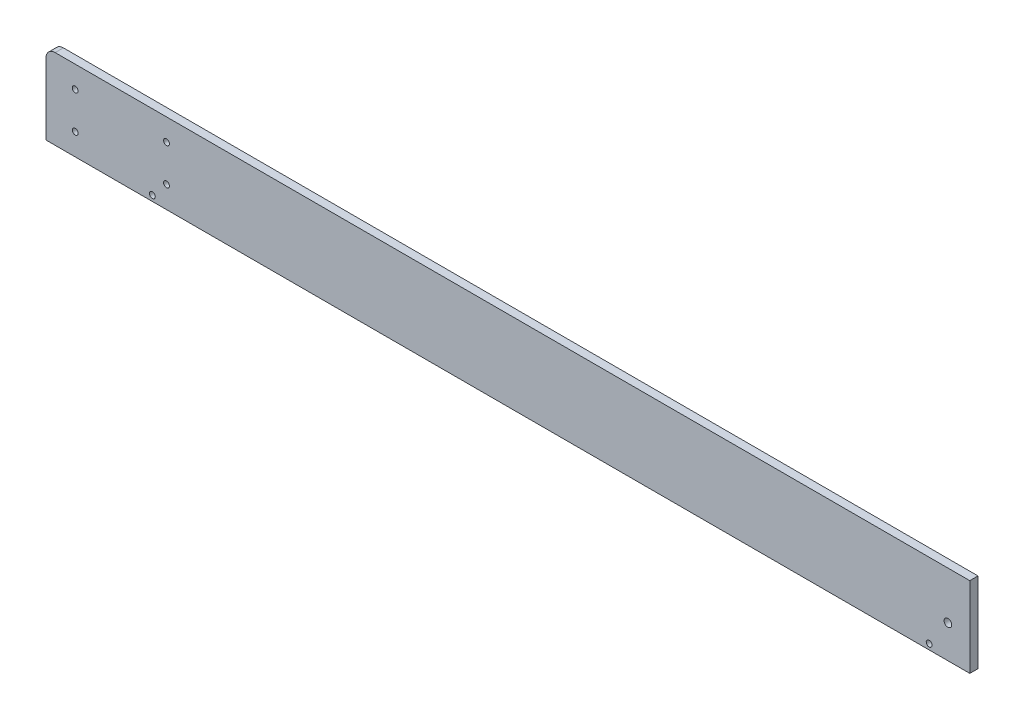
SolidWorks part; units mm, degrees
ref_plane "Front Plane" through (0, 0, 0) normal (0, 0, 1) x (1, 0, 0)
ref_plane "Top Plane" through (0, 0, 0) normal (0, 1, 0) x (1, 0, 0)
ref_plane "Right Plane" through (0, 0, 0) normal (1, 0, 0) x (0, 0, -1)
sketch "Sketch1" plane through (0, 0, 0) normal (0, 0, 1) x (1, 0, 0)
  line L0 (-253, 0) -> (-154.8681, 0) construction
  line L1 (-253, -22) -> (253, -22)
  line L2 (-253, -22) -> (-253, 22)
  line L3 (-253, 22) -> (253, 22)
  line L4 (253, -22) -> (253, 22)
  line L5 (-253, -22) -> (253, 22) construction
  line L6 (-253, 22) -> (253, -22) construction
  line L7 (-247, 6.6679) -> (-247, 39) construction
  circle A0 centre (241, -4) radius 2.1 construction
  circle A1 centre (241, -4) radius 2.1
  circle A2 centre (-237, 10) radius 1.6
  circle A3 centre (-187, 10) radius 1.6
  circle A6 centre (-187, -10) radius 1.6
  circle A9 centre (-237, -10) radius 1.6
  circle A10 centre (230.75, -19) radius 1.6 construction
  circle A11 centre (230.75, -19) radius 1.6
  circle A12 centre (-194.75, -19) radius 1.6 construction
  circle A13 centre (-194.75, -19) radius 1.6
  point P0 (0, 0)
  dimension "D3" = 3.2
  dimension "D1" = 506
  dimension "D2" = 44
  dimension "D4" = 10
  dimension "D5" = 10
  dimension "D6" = 2
  dimension "D7" = 2
extrude "Boss-Extrude1" add sketch "Sketch1" along normal blind 4.5
fillet "Fillet1" radius 5 1 edges at (-253, 22, 2.25)
